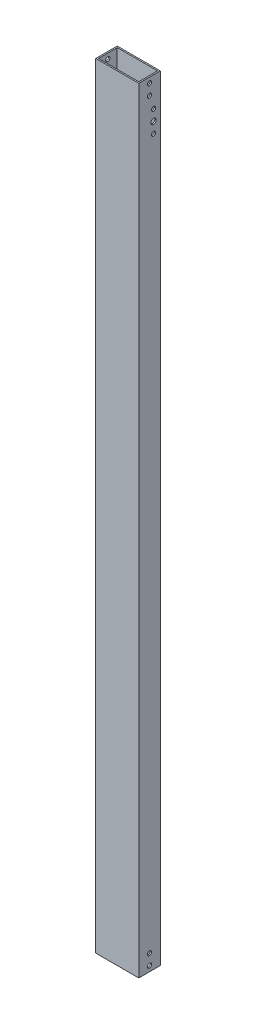
SolidWorks part; units mm, degrees
ref_plane "Front Plane" through (0, 0, 0) normal (0, 0, 1) x (1, 0, 0)
ref_plane "Top Plane" through (0, 0, 0) normal (0, 1, 0) x (1, 0, 0)
ref_plane "Right Plane" through (0, 0, 0) normal (1, 0, 0) x (0, 0, -1)
sketch "Sketch1" plane through (0, 0, 0) normal (0, 0, 1) x (1, 0, 0)
  line L1 (-25.4, -457.2) -> (25.4, -457.2)
  line L2 (-25.4, -457.2) -> (-25.4, 457.2)
  line L3 (-25.4, 457.2) -> (25.4, 457.2)
  line L4 (25.4, -457.2) -> (25.4, 457.2)
  line L5 (-25.4, -457.2) -> (25.4, 457.2) construction
  line L6 (-25.4, 457.2) -> (25.4, -457.2) construction
  point P0 (0, 0)
  dimension "D1" = 50.8
  dimension "D2" = 914.4
extrude "Boss-Extrude1" add sketch "Sketch1" along normal mid plane 25.4
shell "Shell1" thickness 1.5875 removed face at (0, -457.2, 0) removed face at (0, 457.2, 0)
sketch "Sketch3" plane through (0, 0, 0) normal (1, 0, 0) x (0, 0, -1)
  line L0 (-12.7, -457.2) -> (12.7, -457.2) construction
  circle A0 centre (0, -450.85) radius 2.4892
  circle A1 centre (0, -438.15) radius 2.4892
  point P6 (0, -457.2)
  dimension "D1" = 4.9784
  dimension "D2" = 6.35
  dimension "D3" = 12.7
extrude "Cut-Extrude1" cut sketch "Sketch3" against normal through all both and the other way through all
sketch "Sketch4" plane through (0, 0, 0) normal (1, 0, 0) x (0, 0, -1)
  line L0 (12.7, 457.2) -> (12.7, -457.2) construction
  line L3 (-12.7, 457.2) -> (12.7, 457.2) construction
  circle A0 centre (4.7625, 409.575) radius 3.175
  circle A1 centre (4.7625, 422.275) radius 2.4892
  circle A2 centre (4.7625, 396.875) radius 2.4892
  dimension "D1" = 6.35
  dimension "D4" = 4.9784
  dimension "D2" = 7.9375
  dimension "D5" = 12.7
  dimension "D6" = 12.7
  dimension "D3" = 47.625
extrude "Cut-Extrude2" cut sketch "Sketch4" against normal through all both and the other way through all
mirror "Mirror1" about plane through (0, 0, 0) normal (0, 1, 0) of "Cut-Extrude1"
sketch "Sketch5" plane through (0, 0, 0) normal (0, 0, 1) x (1, 0, 0)
  line L1 (-15.875, 423.0688) -> (15.875, 423.0688)
  line L2 (-15.875, 423.0688) -> (-15.875, 396.0813)
  line L3 (-15.875, 396.0813) -> (15.875, 396.0813)
  line L4 (15.875, 423.0688) -> (15.875, 396.0813)
  line L6 (25.4, 457.2) -> (-25.4, 457.2) construction
  point P4 (-15.875, 409.575)
  point P8 (0, 423.0688)
  point P9 (0, 457.2)
  dimension "D1" = 31.75
  dimension "D2" = 26.9875
  dimension "D3" = 47.625
extrude "Cut-Extrude3" cut sketch "Sketch5" against normal through all
fillet "Fillet1" radius 3.175 4 edges at (15.875, 423.0688, -11.9062) (15.875, 396.0813, -11.9062) (-15.875, 396.0813, -11.9062) (-15.875, 423.0688, -11.9062)
equation "\"D6@Sketch4\"=\"D5@Sketch4\""
